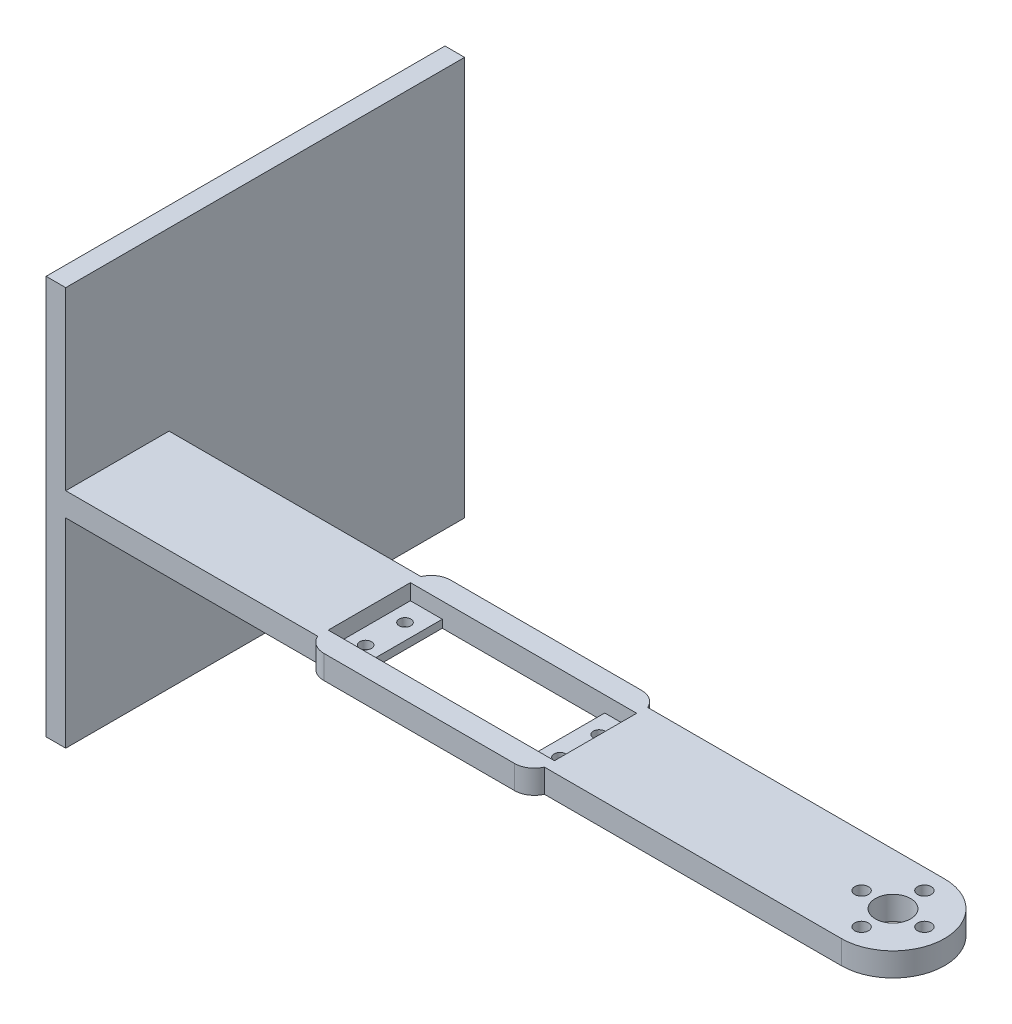
SolidWorks part; units mm, degrees
ref_plane "Front Plane" through (0, 0, 0) normal (0, 0, 1) x (1, 0, 0)
ref_plane "Top Plane" through (0, 0, 0) normal (0, 1, 0) x (1, 0, 0)
ref_plane "Right Plane" through (0, 0, 0) normal (1, 0, 0) x (0, 0, -1)
sketch "Sketch1" plane through (0, 0, 0) normal (0, 1, 0) x (1, 0, 0)
  line L0 (0, 0) -> (0, -8)
  line L3 (-144.1363, -13.1544) -> (-144.1363, 13.1544)
  line L4 (-104.5717, 5) -> (-104.5717, -5) construction
  line L5 (-83.8865, -10.7454) -> (-75.7569, -10.7454)
  line L6 (-129.3217, -5) -> (-79.8217, -5) construction
  line L7 (-129.2967, 5) -> (-79.8467, 5) construction
  line L12 (-83.8865, -10.7454) -> (-83.8865, 10.4665)
  line L13 (-83.8865, 10.4665) -> (-75.7569, 10.4665)
  line L14 (-75.7569, -10.7454) -> (-75.7569, 10.4665)
  line L15 (-83.8865, -10.7454) -> (-75.7569, 10.4665) construction
  line L16 (-83.8865, 10.4665) -> (-75.7569, -10.7454) construction
  line L17 (-125.2569, -10.7454) -> (-133.3865, -10.7454)
  line L18 (-133.3865, -10.7454) -> (-133.3865, 10.4665)
  line L19 (-125.2569, 10.4665) -> (-133.3865, 10.4665)
  line L20 (-125.2569, -10.7454) -> (-125.2569, 10.4665)
  line L21 (-75.7569, 10.4665) -> (-75.7569, -10.7454)
  line L22 (-75.7569, 10.4665) -> (-133.3865, 10.4665)
  line L23 (-75.7569, -10.7454) -> (-133.3865, -10.7454)
  line L24 (-133.3865, 10.4665) -> (-133.3865, -10.7454)
  line L25 (0, 13.1544) -> (-144.1363, 13.1544)
  line L26 (0, -13.1544) -> (-144.1363, -13.1544)
  line L27 (-144.1363, 13.1544) -> (-144.1363, -13.1544)
  line L28 (-144.1363, -13.1544) -> (-202.5563, -13.1544)
  line L29 (-144.1363, 13.1544) -> (-202.5563, 13.1544)
  line L30 (-202.5563, -13.1544) -> (-202.5563, 13.1544)
  line L31 (-202.5563, 0) -> (-197.5563, 0) construction
  line L32 (-202.5563, -13.1544) -> (-197.5563, -13.1544)
  line L33 (-202.5563, -13.1544) -> (-202.5563, 88.4456)
  line L34 (-197.5563, -13.1544) -> (-197.5563, 88.4456)
  line L35 (-202.5563, 88.4456) -> (-197.5563, 88.4456)
  circle A0 centre (0, 0) radius 4.5
  circle A1 centre (0, -8) radius 1.75
  circle A2 centre (-8, 0) radius 1.75
  circle A3 centre (0, 8) radius 1.75
  circle A4 centre (8, 0) radius 1.75
  circle A8 centre (-129.2967, 5) radius 1.5
  circle A9 centre (-129.3217, -5) radius 1.5
  circle A10 centre (-79.8467, 5) radius 1.5
  circle A11 centre (-79.8217, -5) radius 1.5
  arc A12 (0, -13.1544) -> (0, 13.1544) centre (0, 0) ccw
  arc A14 (-75.7569, -10.7454) -> (-73.3479, -13.1544) centre (-75.7569, -13.1544) cw
  arc A15 (-75.7569, 10.4665) -> (-73.0691, 13.1544) centre (-75.7569, 13.1544) ccw
  point P7 (13.1544, 0)
  point P14 (0, 0)
  point P19 (-79.8217, -0.1394)
  point P45 (-200.0563, 88.4456)
  dimension "D1" = 9
  dimension "D3" = 3.5
  dimension "D7" = 5
  dimension "D10" = 3
  dimension "D11" = 3
  dimension "D14" = 3
  dimension "D15" = 3
  dimension "D2" = 8
  dimension "D5" = 157.2907
  dimension "D6" = 58.42
  dimension "D8" = 101.6
  dimension "D12" = 49.5
  dimension "D13" = 49.45
  dimension "D16" = 10
  dimension "D4" = 4
extrude "Boss-Extrude1" add sketch "Sketch1" along normal blind 6 contours L34 L28 L3 L29 | L13 A15 L25 L3 L26 A14 L5 L23 L17 L18 L19 L22 | A15 L14 A14 L26 A12 L25 A1 A0 A2 A3 A4 region at (-170.8463, 0, 0) region at (-143.3785, 0, 0) region at (-34.0123, 0, 0.006)
extrude "Boss-Extrude2" add sketch "Sketch1<22>" along normal blind 2 contours L17 L20 L19 L18 A9 A8 | L5 L14 L13 L12 A11 A10 region at (-79.8206, 0, 0.1519) region at (-129.3228, 0, 0.1519)
sketch "Sketch1<22>" plane through (0, 0, 0) normal (0, 1, 0) x (1, 0, 0) same geometry as "Sketch1"
extrude "Boss-Extrude3" add sketch "Sketch1<23>" along normal blind 50.8 and the other way blind 50.8 contours L35 L33 L29 L34 | L28 L34 L29 L30 region at (-200.0563, 0, 0) region at (-200.0563, 0, -50.8)
sketch "Sketch1<23>" plane through (0, 0, 0) normal (0, 1, 0) x (1, 0, 0) same geometry as "Sketch1"
sketch "Sketch3" plane through (0, 6, 0) normal (0, 1, 0) x (1, 0, 0)
  line L0 (-133.3865, -10.7454) -> (-133.3865, -37.2112) construction
  line L1 (-75.7569, -10.7454) -> (-75.7569, -28.7695) construction
  line L2 (13.1544, 0) -> (-155.7689, 0) construction
  arc A0 (0, -13.1544) -> (0, 13.1544) centre (0, 0) ccw construction
sketch "Sketch4" plane through (0, 0, 13.1544) normal (0, 0, 1) x (1, 0, 0)
  line L0 (-133.384, 6) -> (-133.384, 0) construction
  line L1 (0, 6) -> (-197.5563, 6) construction
  line L2 (0, 0) -> (-197.5563, 0) construction
  line L3 (-75.635, 6) -> (-75.635, 0) construction
  line L5 (-133.384, 0) -> (-75.635, 0)
  line L6 (-133.384, 0) -> (-133.384, 6)
  line L7 (-133.384, 6) -> (-75.635, 6)
  line L8 (-75.635, 0) -> (-75.635, 6)
extrude "Boss-Extrude4" add sketch "Sketch4" along normal blind 3
fillet "Fillet2" radius 5 2 edges at (-75.635, 3, 16.1544) (-133.384, 3, 16.1544)
ref_plane "Plane1" through (0, 0, 0) normal (0, 0, -1) x (-1, 0, 0)
mirror "Mirror1" about plane through (0, 0, 0) normal (0, 0, -1) of "Boss-Extrude1", "Fillet2", "Boss-Extrude4"
